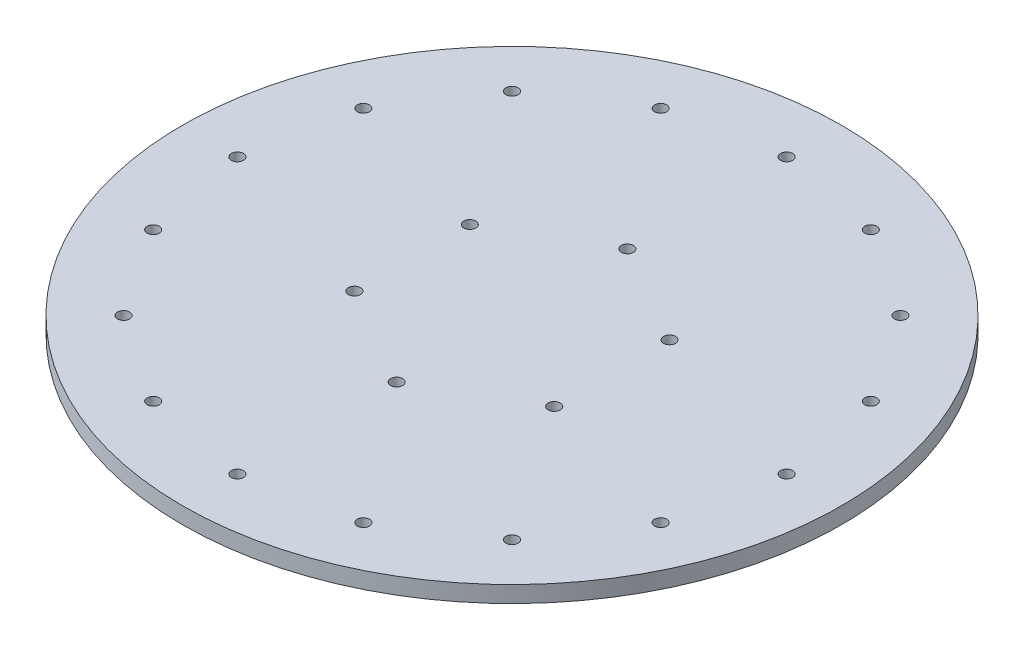
SolidWorks part; units mm, degrees
ref_plane "Front Plane" through (0, 0, 0) normal (0, 0, 1) x (1, 0, 0)
ref_plane "Top Plane" through (0, 0, 0) normal (0, 1, 0) x (1, 0, 0)
ref_plane "Right Plane" through (0, 0, 0) normal (1, 0, 0) x (0, 0, -1)
sketch "Sketch1" plane through (0, 0, 0) normal (0, 1, 0) x (1, 0, 0)
  circle A0 centre (0, 0) radius 300
  dimension "D1" = 600
extrude "Boss-Extrude1" add sketch "Sketch1" along normal blind 15
sketch "Extrusion Hole locations" plane through (0, 0, 0) normal (0, 1, 0) x (1, 0, 0)
  point P0 (0, 105)
  point P1 (90.9327, 52.5)
  point P3 (0, 250)
  point P4 (90.9327, -52.5)
  point P7 (0, -105)
  point P8 (-90.9327, -52.5)
  point P9 (-90.9327, 52.5)
  point P14 (95.6709, 230.9699)
  point P15 (176.7767, 176.7767)
  point P16 (230.9699, 95.6709)
  point P17 (250, 0)
  point P18 (230.9699, -95.6709)
  point P19 (176.7767, -176.7767)
  point P20 (95.6709, -230.9699)
  point P21 (0, -250)
  point P22 (-95.6709, -230.9699)
  point P23 (-176.7767, -176.7767)
  point P24 (-230.9699, -95.6709)
  point P25 (-250, 0)
  point P26 (-230.9699, 95.6709)
  point P27 (-176.7767, 176.7767)
  point P28 (-95.6709, 230.9699)
  dimension "D1" = 105
  dimension "D2" = 250
  dimension "D3" = 6
  dimension "D4" = 16
hole_wizard "CBORE for M10 Hex Head Bolt1" positions "Extrusion Hole locations" profile "Sketch3" counterbore size "M10" standard "ANSI Metric" end condition through all
sketch "Sketch3" plane through (0, 0, -105) normal (1, 0, 0) x (0, 0, -1)
  line L0 (0, 0) -> (0, 15)
  line L1 (0, 15) -> (5.5, 15)
  line L3 (5.5, 15) -> (5.5, 6.85)
  line L4 (5.5, 6.85) -> (10.74, 6.85)
  line L5 (10.74, 6.85) -> (10.74, 0)
  line L7 (10.74, 0) -> (0, 0)
  line L11 (0, -6.35) -> (0, 107.95) construction
  dimension "Thru Hole Dia." = 11
  dimension "Thru Hole Depth" = 15
  dimension "C'Bore Dia." = 21.48
  dimension "C'Bore Depth" = 6.85
